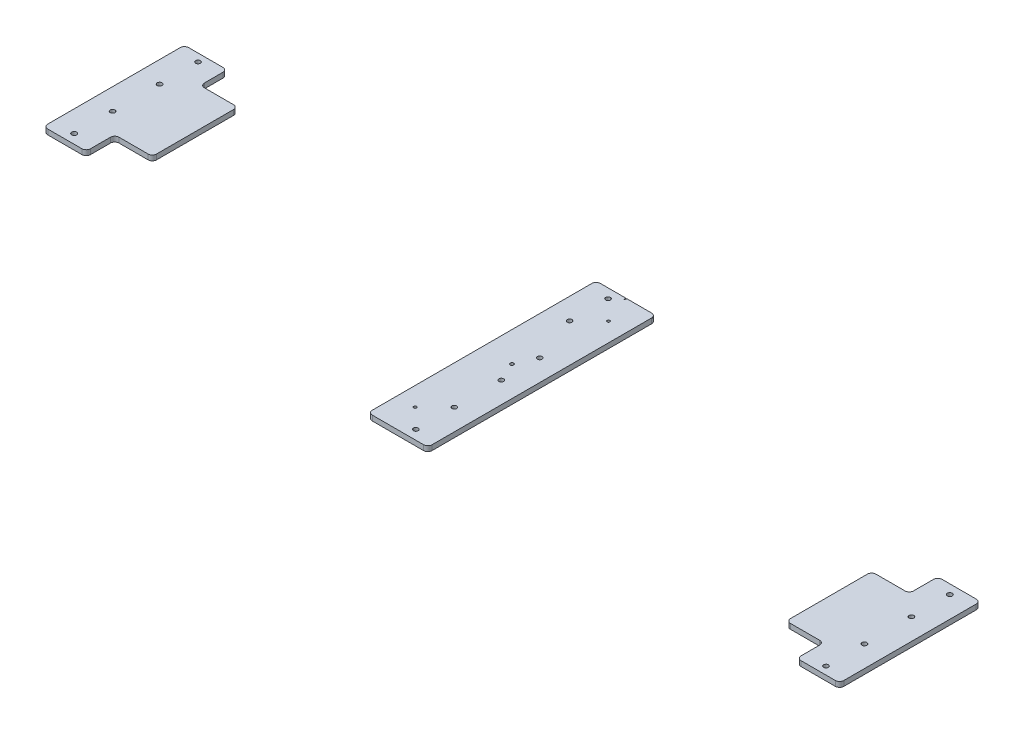
SolidWorks part; units mm, degrees
material "Plain Carbon Steel"
ref_plane "Front Plane" through (0, 0, 0) normal (0, 0, 1) x (1, 0, 0)
ref_plane "Top Plane" through (0, 0, 0) normal (0, 1, 0) x (1, 0, 0)
ref_plane "Right Plane" through (0, 0, 0) normal (1, 0, 0) x (0, 0, -1)
sketch "Sketch3" plane through (0, -250.1022, 0) normal (0, 1, 0) x (-1, 0, 0)
  line L0 (0, -248.3621) -> (0, -253.3621)
  line L1 (-35.0076, 312.7061) -> (-34.9894, 315.6379)
  line L6 (34.9796, 315.6379) -> (34.9796, 48.6379)
  line L7 (34.9796, 48.6379) -> (-0.0049, 48.6379)
  line L8 (-34.9894, 48.6379) -> (-34.9894, 315.6379)
  line L9 (-34.9894, 315.6379) -> (34.9796, 315.6379)
  line L10 (514.9951, 215.547) -> (514.9951, 50.547)
  line L11 (514.9951, 50.547) -> (464.9951, 50.5561)
  line L12 (464.9951, 50.5561) -> (464.9951, 215.5561)
  line L13 (464.9951, 215.5561) -> (514.9951, 215.547)
  line L14 (-0.0049, 48.6379) -> (-0.0049, 315.6379) construction
  line L15 (-1.2474, 48.6379) -> (-0.0049, 52.1379)
  line L16 (-490.0054, 162.4634) -> (-490.0049, 159.5781) construction
  line L17 (464.9951, 182.6303) -> (464.9951, 83.4819)
  line L22 (416.9951, 167.1379) -> (464.9951, 167.1379)
  line L24 (464.9951, 182.6303) -> (464.9951, 83.4819)
  line L26 (416.9951, 167.1379) -> (416.9951, 97.1379)
  line L27 (416.9951, 97.1379) -> (464.9951, 97.1379)
  line L28 (464.9951, 167.1379) -> (464.9951, 97.1379)
  line L29 (-0.0001, -250.8621) -> (-0.0069, 182.1379) construction
  line L30 (-10.0049, 259.6379) -> (-538.757, 259.6379) construction
  line L31 (9.9951, 59.6379) -> (9.9951, 104.6379) construction
  line L32 (-490.0136, 207.3015) -> (-490.0131, 204.5188) construction
  line L33 (489.9951, 59.6379) -> (489.9951, 104.6379) construction
  line L34 (489.9951, 104.6379) -> (489.9951, 159.6675) construction
  line L35 (489.9951, 159.6675) -> (489.9951, 204.6083) construction
  line L36 (420.9951, 97.1379) -> (420.9951, 167.1379)
  line L37 (-515.0029, 148.6348) -> (-515.033, 313.6348)
  line L38 (420.9951, 97.1379) -> (464.9951, 97.1379)
  line L39 (420.9951, 97.1379) -> (420.9951, 82.1379)
  line L40 (420.9951, 82.1379) -> (464.9951, 82.1379)
  line L41 (464.9951, 97.1379) -> (464.9951, 82.1379)
  line L42 (420.9951, 167.1379) -> (464.9951, 167.1379)
  line L43 (420.9951, 167.1379) -> (420.9951, 182.1379)
  line L44 (420.9951, 182.1379) -> (464.9951, 182.1379)
  line L45 (464.9951, 167.1379) -> (464.9951, 182.1379)
  line L46 (-515.033, 313.6348) -> (-465.033, 313.6348)
  line L47 (-465.033, 313.6348) -> (-465.0029, 148.6348)
  line L48 (-465.0029, 148.6348) -> (-515.0029, 148.6348)
  line L49 (-465.0089, 181.5606) -> (-465.027, 280.709)
  line L50 (-417.0117, 197.0618) -> (-465.0117, 197.053)
  line L51 (-465.0089, 181.5606) -> (-465.027, 280.709)
  line L52 (-417.0117, 197.0618) -> (-417.0245, 267.0618)
  line L53 (-417.0245, 267.0618) -> (-465.0245, 267.053)
  line L54 (-465.0117, 197.053) -> (-465.0245, 267.053)
  line L55 (-421.0245, 267.0611) -> (-421.0117, 197.0611)
  line L56 (-421.0245, 267.0611) -> (-465.0245, 267.053)
  line L57 (-421.0245, 267.0611) -> (-421.0272, 282.0611)
  line L58 (-421.0272, 282.0611) -> (-465.0272, 282.053)
  line L59 (-465.0245, 267.053) -> (-465.0272, 282.053)
  line L60 (-421.0117, 197.0611) -> (-465.0117, 197.053)
  line L61 (-421.0117, 197.0611) -> (-421.009, 182.0611)
  line L62 (-421.009, 182.0611) -> (-465.009, 182.053)
  line L63 (-465.0117, 197.053) -> (-465.009, 182.053)
  line L64 (-490.0313, 304.5485) -> (-490.0308, 301.8107) construction
  line L65 (-490.0231, 259.5485) -> (-490.0226, 256.7211) construction
  line L66 (-490.0131, 204.5188) -> (-490.0126, 201.7362) construction
  line L67 (489.9951, 82.1379) -> (-490.0967, 82.1379) construction
  line L68 (489.9951, 182.1379) -> (-538.7812, 182.1379) construction
  line L69 (-13.7537, 282.1379) -> (-538.757, 282.1379) construction
  line L70 (-10.0049, 159.6379) -> (-10.0049, 204.6379) construction
  line L71 (-490.0236, 262.3758) -> (-490.0231, 259.5485) construction
  line L72 (-490.0049, 159.5781) -> (-490.0049, 331.2642) construction
  line L73 (-10.0049, 304.6379) -> (-538.7814, 304.6379) construction
  line L74 (-10.0049, 159.6379) -> (-538.7814, 159.6379) construction
  line L75 (-10.0049, 204.6379) -> (-538.7814, 204.6379) construction
  line L76 (9.9951, 59.6379) -> (551.1029, 59.6379) construction
  line L77 (9.9951, 104.6379) -> (551.1029, 104.6379) construction
  line L78 (-10.0049, 159.6379) -> (551.103, 159.6379) construction
  line L79 (-10.0049, 204.6379) -> (551.1029, 204.6379) construction
  line L80 (-0.0049, 48.6379) -> (-0.0049, 52.1379)
  line L81 (-13.7537, 282.1379) -> (18.9975, 282.632) construction
  line L82 (-10.0049, 204.6379) -> (-10.0049, 309.211) construction
  line L83 (-1.2474, 48.6379) -> (-34.9894, 48.6379)
  arc A0 (0, -253.3621) -> (0, -248.3621) centre (-0.0001, -250.8621) ccw
  circle A1 centre (489.9951, 59.6379) radius 2.7378
  circle A2 centre (489.9951, 104.6379) radius 2.8274
  circle A3 centre (489.9951, 159.6675) radius 2.7826
  circle A4 centre (489.9951, 204.6083) radius 2.8853
  circle A5 centre (9.9951, 59.6379) radius 2.75
  circle A6 centre (9.9951, 104.6379) radius 2.75
  circle A7 centre (-10.0049, 159.6379) radius 2.75
  circle A8 centre (-10.0049, 204.6379) radius 2.75
  circle A9 centre (-10.0049, 259.6379) radius 2.75
  circle A10 centre (-10.0049, 304.6379) radius 2.75
  circle A15 centre (12.9951, 282.5442) radius 1.65
  circle A16 centre (-13.0049, 82.1379) radius 1.65
  circle A18 centre (-490.0313, 304.5485) radius 2.7378
  circle A19 centre (-490.0231, 259.5485) radius 2.8274
  circle A20 centre (-490.0131, 204.5188) radius 2.7826
  circle A21 centre (-490.0049, 159.5781) radius 2.8853
  circle A22 centre (-0.0069, 182.1379) radius 2
  point P26 (-0.0049, 182.1379)
  point P56 (464.9951, 133.0561)
  point P67 (-13.7537, 282.1379)
  point P82 (-465.0179, 231.1348)
  point P95 (-0.0069, 182.1379)
  dimension "D7" = 3.3
  dimension "D8" = 3.3
  dimension "D4" = 22.5
  dimension "D1" = 10
  dimension "D2" = 10
  dimension "D3" = 2
  dimension "D5" = 165
  dimension "D6" = 22.5
  dimension "D9" = 22.5
  dimension "D10" = 13
  dimension "D11" = 22.5
  dimension "D12" = 22.5
  dimension "D13" = 11
  dimension "D14" = 55
  dimension "D15" = 22.5
  dimension "D16" = 55
  dimension "D17" = 13
  dimension "D18" = 25
  dimension "D19" = 25
  dimension "D20" = 70
  dimension "D21" = 44
  dimension "D22" = 4
  dimension "D23" = 15
  dimension "D24" = 15
  dimension "D25" = 433
  dimension "D26" = 11
  dimension "D29" = 490
  dimension "D30" = 490
extrude "Boss-Extrude1" add sketch "Sketch3" along normal blind 6 contours L13 L12 L17 L24 L11 L10 A4 A3 A2 A1 | L39 L40 L12 L27 | L36 L27 L24 L22 | L44 L43 L22 L17 L12 | L62 L61 L50 L49 L47 | L55 L53 L51 L50 | L57 L58 L47 L53 | L48 L47 L49 L51 L46 L37 A21 A20 A19 A18 | A22 L14 L7 L6 L9 A15 A6 A5 | A22 L14 L9 L1 L8 L7 L15 A16 A10 A9 A8 A7 region at (-32.2194, -250.1022, 182.1379) region at (-489.9951, -250.1022, 133.0422) region at (-442.9951, -250.1022, 89.6379) region at (-442.9951, -250.1022, 174.6379) region at (-442.9951, -250.1022, 132.1379) region at (490.0179, -250.1022, 231.1442) region at (443.0259, -250.1022, 274.557) region at (443.0104, -250.1022, 189.557) region at (443.0181, -250.1022, 232.057)
fillet "Fillet1" radius 5 8 edges at (-514.9951, -247.1022, 50.547) (-464.9951, -247.1022, 50.5561) (-464.9951, -247.1022, 215.5561) (-514.9951, -247.1022, 215.547) (-464.9951, -247.1022, 82.1379) (-420.9951, -247.1022, 82.1379) (-420.9951, -247.1022, 182.1379) (-464.9951, -247.1022, 182.1379)
fillet "Fillet2" radius 5 8 edges at (421.009, -247.1022, 182.0611) (421.0272, -247.1022, 282.0611) (465.0272, -247.1022, 282.053) (465.009, -247.1022, 182.053) (465.0029, -247.1022, 148.6348) (515.0029, -247.1022, 148.6348) (465.033, -247.1022, 313.6348) (515.033, -247.1022, 313.6348)
fillet "Fillet3" radius 5 4 edges at (-34.9796, -247.1022, 48.6379) (-34.9796, -247.1022, 315.6379) (34.9894, -247.1022, 315.6379) (34.9894, -247.1022, 48.6379)
